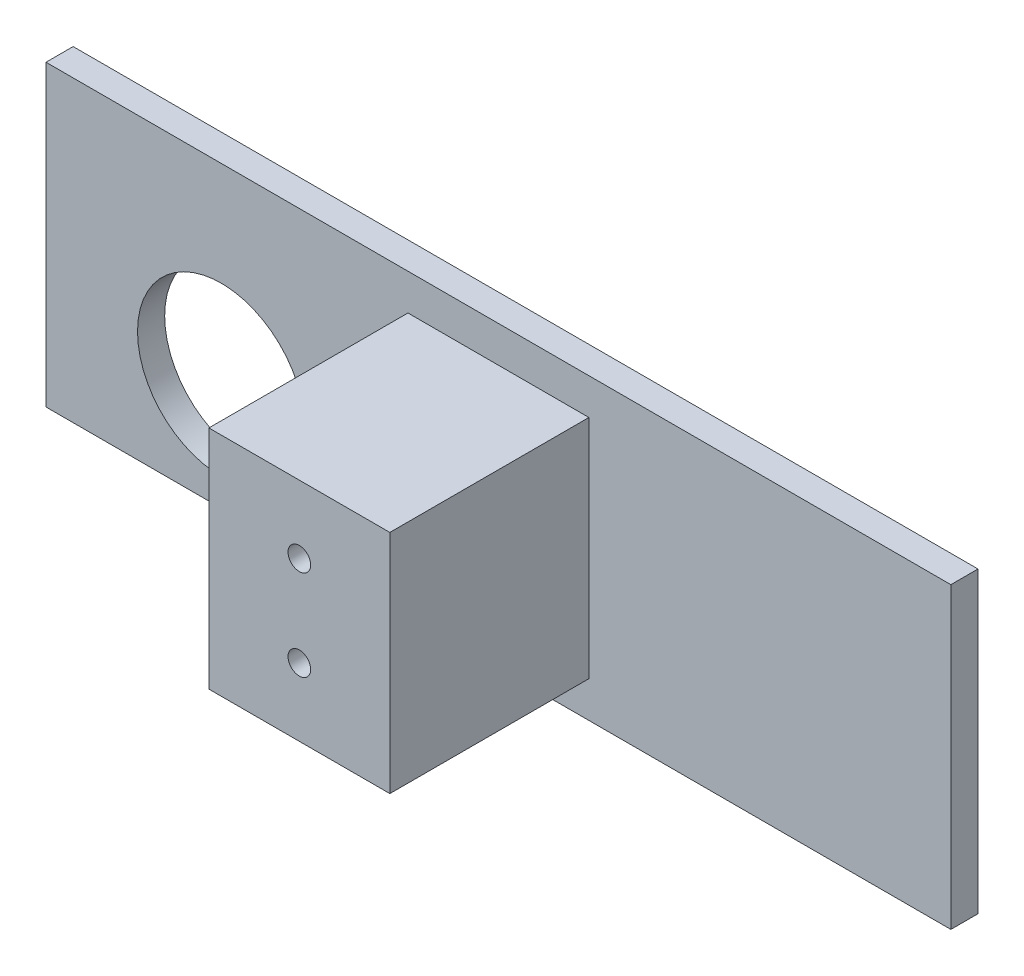
SolidWorks part; units mm, degrees
ref_plane "Plan de face" through (0, 0, 0) normal (0, 0, 1) x (1, 0, 0)
ref_plane "Plan de dessus" through (0, 0, 0) normal (0, 1, 0) x (1, 0, 0)
ref_plane "Plan de droite" through (0, 0, 0) normal (1, 0, 0) x (0, 0, -1)
sketch "Esquisse1" plane through (0, 0, 0) normal (0, 0, 1) x (1, 0, 0)
  line L1 (-12.2348, 13.2576) -> (7.7652, 13.2576)
  line L2 (-12.2348, 13.2576) -> (-12.2348, -11.7424)
  line L3 (-12.2348, -11.7424) -> (7.7652, -11.7424)
  line L4 (7.7652, 13.2576) -> (7.7652, -11.7424)
  dimension "D1" = 20
  dimension "D2" = 25
extrude "Boss.-Extru.1" add sketch "Esquisse1" along normal blind 22
sketch "Esquisse2" plane through (0, 0, 22) normal (0, 0, 1) x (1, 0, 0)
  line L0 (-12.2348, 0.7576) -> (7.7652, 0.7576) construction
  line L1 (-12.2348, 13.2576) -> (-12.2348, -11.7424) construction
  line L2 (7.7652, -11.7424) -> (7.7652, 13.2576) construction
  line L3 (-2.2348, 5.7576) -> (-2.2348, -4.2424) construction
  circle A0 centre (-2.2348, 5.7576) radius 1.25
  circle A1 centre (-2.2348, -4.2424) radius 1.25
  point P13 (-2.2348, 0.7576)
  point P14 (-2.2348, 0.7576)
  dimension "D2" = 2.5
  dimension "D1" = 10
extrude "Enlèv. mat.-Extru.1" cut sketch "Esquisse2" against normal blind 15
sketch "Esquisse3" plane through (0, 0, 0) normal (0, 0, -1) x (-1, 0, 0)
  line L1 (52.2348, -15.7424) -> (-47.7652, -15.7424)
  line L2 (52.2348, -15.7424) -> (52.2348, 17.2576)
  line L3 (52.2348, 17.2576) -> (-47.7652, 17.2576)
  line L4 (-47.7652, -15.7424) -> (-47.7652, 17.2576)
  line L5 (-7.7652, 13.2576) -> (12.2348, 13.2576) construction
  line L7 (12.2348, -11.7424) -> (-7.7652, -11.7424) construction
  line L8 (12.2348, 13.2576) -> (12.2348, -11.7424) construction
  line L9 (-7.7652, -11.7424) -> (-7.7652, 13.2576) construction
  dimension "D1" = 4
  dimension "D2" = 40
  dimension "D3" = 40
  dimension "D4" = 4
extrude "Boss.-Extru.2" add sketch "Esquisse3" along normal blind 3
sketch "Esquisse4" plane through (0, 0, -3) normal (0, 0, -1) x (-1, 0, 0)
  line L0 (52.2348, -15.7424) -> (52.2348, 17.2576) construction
  line L1 (-47.7652, -15.7424) -> (52.2348, -15.7424) construction
  circle A0 centre (32.8698, -3.4521) radius 9.25
  dimension "D1" = 18.5
  dimension "D2" = 19.365
  dimension "D3" = 12.2903
extrude "Enlèv. mat.-Extru.2" cut sketch "Esquisse4" against normal up to next
